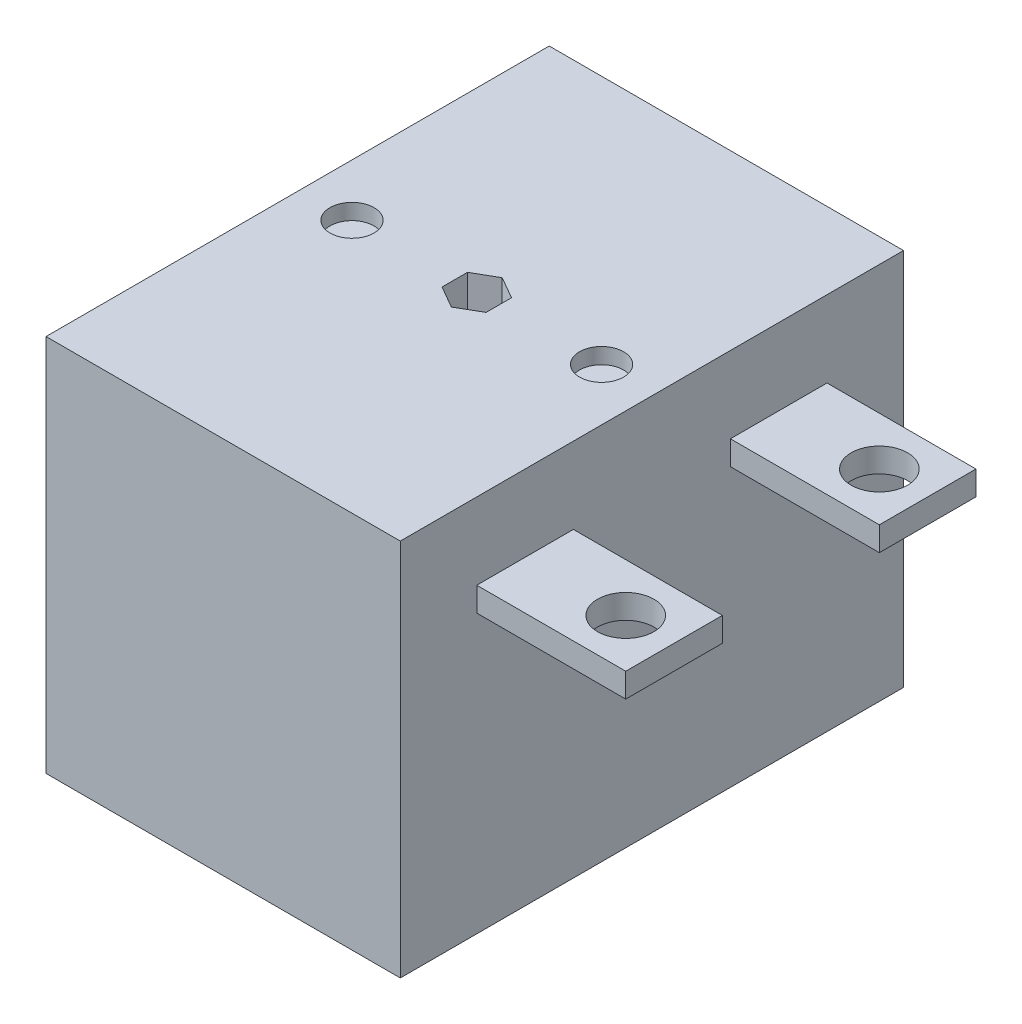
SolidWorks part; units mm, degrees
ref_plane "Front Plane" through (0, 0, 0) normal (0, 0, 1) x (1, 0, 0)
ref_plane "Top Plane" through (0, 0, 0) normal (0, 1, 0) x (1, 0, 0)
ref_plane "Right Plane" through (0, 0, 0) normal (1, 0, 0) x (0, 0, -1)
sketch "Sketch1" plane through (0, 0, 0) normal (0, 0, 1) x (1, 0, 0)
  line L1 (0, 0) -> (22.352, 0)
  line L2 (0, 0) -> (0, 23.876)
  line L3 (0, 23.876) -> (22.352, 23.876)
  line L4 (22.352, 0) -> (22.352, 23.876)
  dimension "D1" = 23.876
  dimension "D2" = 22.352
extrude "Boss-Extrude1" add sketch "Sketch1" along normal blind 31.75 contours L2 L3 L4 L1
sketch "Sketch2" plane through (0, 23.876, 0) normal (0, 1, 0) x (1, 0, 0)
  line L0 (0, -31.75) -> (22.352, -31.75) construction
  line L1 (11.176, -17.352) -> (12.5651, -16.55)
  line L2 (12.5651, -16.55) -> (12.5651, -14.946)
  line L3 (12.5651, -14.946) -> (11.176, -14.144)
  line L4 (11.176, -14.144) -> (9.7869, -14.946)
  line L5 (9.7869, -14.946) -> (9.7869, -16.55)
  line L6 (9.7869, -16.55) -> (11.176, -17.352)
  line L7 (0, -31.75) -> (0, 0) construction
  circle A0 centre (11.176, -15.748) radius 2.5
  circle A1 centre (11.176, -15.748) radius 1.3891 construction
  circle A2 centre (3.302, -15.748) radius 1.3891
  circle A3 centre (19.05, -15.748) radius 1.3891
  dimension "D1" = 2.7781
  dimension "D2" = 5
  dimension "D3" = 16.002
  dimension "D4" = 11.176
  dimension "D5" = 3.302
  dimension "D6" = 19.05
  dimension "D7" = 11.176
extrude "Cut-Extrude1" cut sketch "Sketch2" against normal blind 4.572 contours L5 L6 L1 L2 L3 L4 region at (11.176, 23.876, 15.748)
extrude "Cut-Extrude2" cut sketch "Sketch2<3>" against normal blind 1 contours A3 | A2 region at (3.302, 23.876, 15.748) region at (19.05, 23.876, 15.748)
sketch "Sketch2<3>" plane through (0, 23.876, 0) normal (0, 1, 0) x (1, 0, 0) same geometry as "Sketch2"
sketch "Sketch4" plane through (22.352, 0, 0) normal (1, 0, 0) x (0, 0, -1)
  line L0 (-31.75, 23.876) -> (0, 23.876) construction
  line L1 (-26.924, 19.05) -> (-20.828, 19.05)
  line L2 (-26.924, 19.05) -> (-26.924, 17.526)
  line L3 (-26.924, 17.526) -> (-20.828, 17.526)
  line L4 (-20.828, 19.05) -> (-20.828, 17.526)
  line L5 (-10.922, 19.05) -> (-4.826, 19.05)
  line L6 (-10.922, 19.05) -> (-10.922, 17.526)
  line L7 (-10.922, 17.526) -> (-4.826, 17.526)
  line L8 (-4.826, 19.05) -> (-4.826, 17.526)
  line L9 (-31.75, 0) -> (-31.75, 23.876) construction
  line L10 (0, 0) -> (0, 23.876) construction
  dimension "D1" = 6.096
  dimension "D2" = 1.524
  dimension "D3" = 4.826
  dimension "D4" = 4.826
  dimension "D5" = 4.826
extrude "Boss-Extrude2" add sketch "Sketch4" along normal blind 9.398
sketch "Sketch5" plane through (0, 19.05, 0) normal (0, 1, 0) x (1, 0, 0)
  line L0 (0, -31.75) -> (22.352, -31.75) construction
  line L5 (0, -31.75) -> (0, 0) construction
  circle A0 centre (28.702, -23.876) radius 1.778
  circle A1 centre (28.702, -7.874) radius 1.778
  dimension "D2" = 3.556
  dimension "D1" = 7.874
  dimension "D3" = 28.702
  dimension "D4" = 23.876
  dimension "D5" = 28.702
extrude "Cut-Extrude3" cut sketch "Sketch5" against normal up to next
